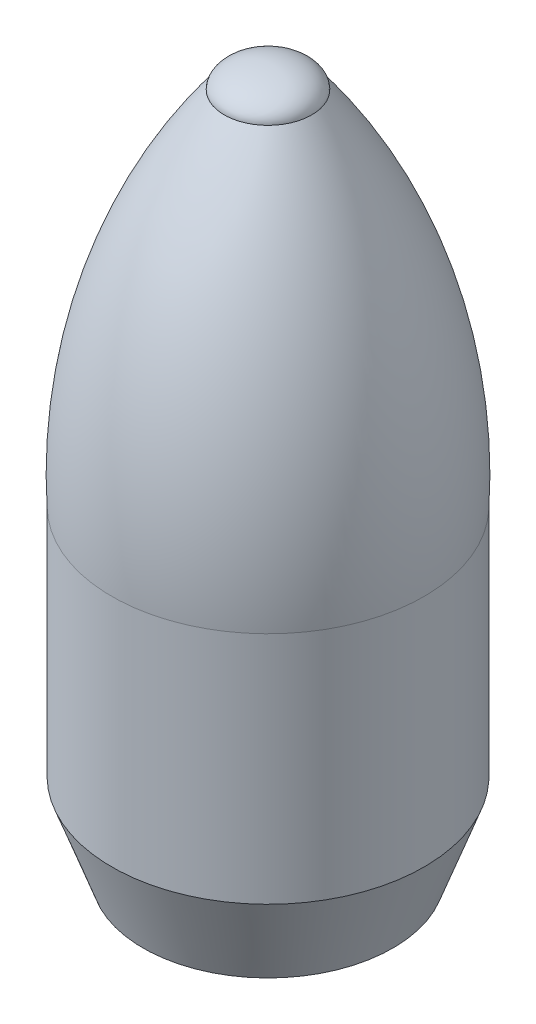
SolidWorks part; units mm, degrees
ref_plane "Front Plane" through (0, 0, 0) normal (0, 0, 1) x (1, 0, 0)
ref_plane "Top Plane" through (0, 0, 0) normal (0, 1, 0) x (1, 0, 0)
ref_plane "Right Plane" through (0, 0, 0) normal (1, 0, 0) x (0, 0, -1)
sketch "Sketch1" plane through (0, 0, 0) normal (0, 0, 1) x (1, 0, 0)
  line L0 (0, -5659.2654) -> (0, 5659.2654) construction
  line L1 (-5659.2654, 0) -> (5659.2654, 0) construction
  line L2 (0, 0) -> (2000, 0)
  line L3 (2000, 0) -> (2500, 1375)
  line L4 (2500, 1375) -> (2500, 5125)
  line L5 (0, 11250) -> (2000, 11250) construction
  line L6 (0, 10900) -> (700, 10900)
  line L7 (0, 0) -> (0, 10900)
  arc A1 (700, 10900) -> (2500, 5125) centre (-6237.3719, 5569.6828) cw
  point P4 (0, 0)
  point P8 (0, 0)
  dimension "D5" = 350
  dimension "D1" = 2000
  dimension "D2" = 2500
  dimension "D3" = 1375
  dimension "D4" = 11250
revolve "Revolve2" add sketch "Sketch1" angle 360 about L7
dome "Dome1" faces to dome 1 distance 350 reverse direction no elliptical dome yes face at (0, 10900, -700) parameters "D1"=350
